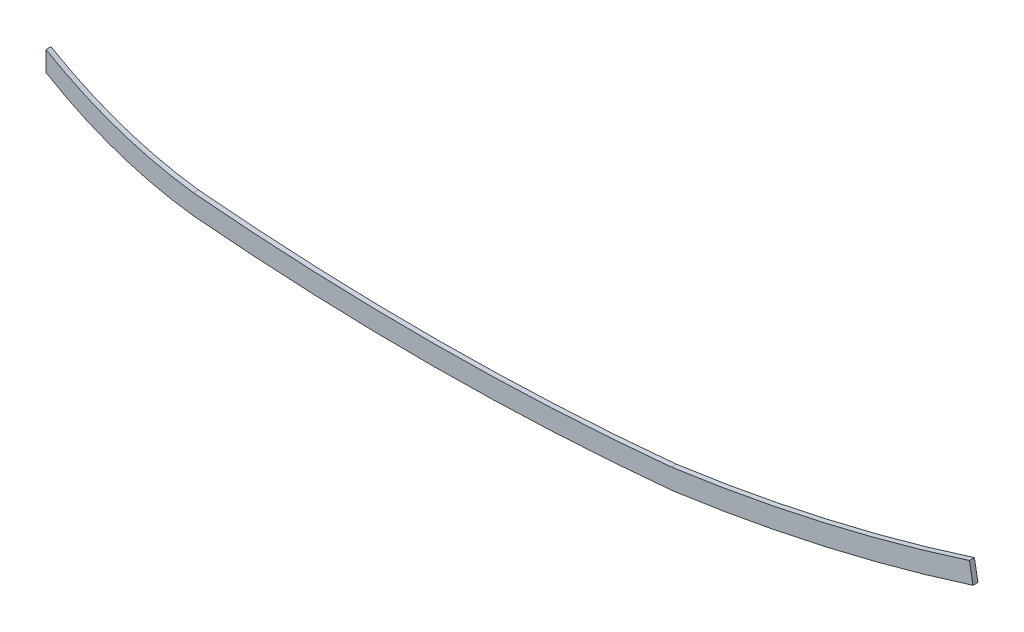
SolidWorks part; units mm, degrees
material "Balsa"
ref_plane "Front Plane" through (0, 0, 0) normal (0, 0, 1) x (1, 0, 0)
ref_plane "Top Plane" through (0, 0, 0) normal (0, 1, 0) x (1, 0, 0)
ref_plane "Right Plane" through (0, 0, 0) normal (1, 0, 0) x (0, 0, -1)
sketch "Sketch2" plane through (0, 0, 0) normal (0, 0, 1) x (1, 0, 0)
  line L0 (0, -93.726) -> (0, -81.026)
  line L2 (93.98, 0) -> (93.98, -379.755) construction
  line L3 (398.3737, -110.9898) -> (402.5381, -142.3403) construction
  line L4 (398.3737, -110.9898) -> (366.1948, 131.2634) construction
  line L7 (590.8643, -81.3536) -> (588.579, -68.7797)
  line L8 (0, 0) -> (672.417, 0) construction
  arc A0 (0, -93.726) -> (93.98, -125.8052) centre (121.8415, 109.5207) ccw
  arc A1 (93.98, -125.8052) -> (400.2036, -124.7658) centre (241.5116, 1518.5899) ccw
  arc A2 (400.2036, -124.7658) -> (590.8643, -81.3536) centre (242.7057, 1007.3312) ccw
  arc A3 (95.6211, -113.2301) -> (398.7207, -112.1786) centre (241.5116, 1518.5899) ccw construction
  arc A4 (93.9818, -113.0827) -> (398.7207, -112.1786) centre (241.5116, 1518.5899) ccw
  arc A5 (398.7207, -112.1786) -> (588.579, -68.7797) centre (242.7057, 1007.3312) ccw
  arc A6 (94.4927, -125.8512) -> (400.2036, -124.7658) centre (241.5116, 1518.5899) ccw construction
  arc A7 (398.7207, -112.1786) -> (587.0046, -69.2844) centre (242.7057, 1007.3312) ccw construction
  arc A9 (0, -81.026) -> (93.9818, -113.0827) centre (124.7234, 130.8365) ccw
  spline S0 degree 3 poles (3.7499, -94.8626) (10.597, -99.2271) (17.6385, -103.1401) (32.0968, -110.0953) (39.5136, -113.1375) (50.922, -117.0433) (54.7721, -118.2354) (60.6197, -119.8556) (62.5829, -120.3681) (66.5243, -121.3341) (68.5001, -121.787) (78.4043, -123.9021) (86.408, -125.1172) (94.4926, -125.8525) knots 0 0 0 0 0.25 0.25 0.5 0.5 0.625 0.625 0.6875 0.6875 0.75 0.75 1 1 1 1 construction
  spline S1 degree 3 poles (94.4926, -125.8525) (120.9278, -128.4258) (173.8258, -132.179) (226.7788, -133.168) (266.5142, -132.8729) (279.7628, -132.6016) (299.6408, -131.9345) (306.2677, -131.6688) (319.5231, -131.0505) (326.1536, -130.6977) (359.2877, -128.7173) (385.6949, -126.4433) (412.003, -123.4859) knots 0 0 0 0 0.25 0.5 0.5 0.625 0.625 0.6875 0.6875 0.75 0.75 1 1 1 1 construction
  dimension "D3" = 236.9696
  dimension "D4" = 1651
  dimension "D5" = 1143
  dimension "D6" = 79.699
  dimension "D7" = 1638.3286
  dimension "D8" = 245.8488
  dimension "D1" = 12.7
  dimension "D2" = 93.726
  dimension "D9" = 93.9818
extrude "Boss-Extrude1" add sketch "Sketch2" along normal blind 3.175
